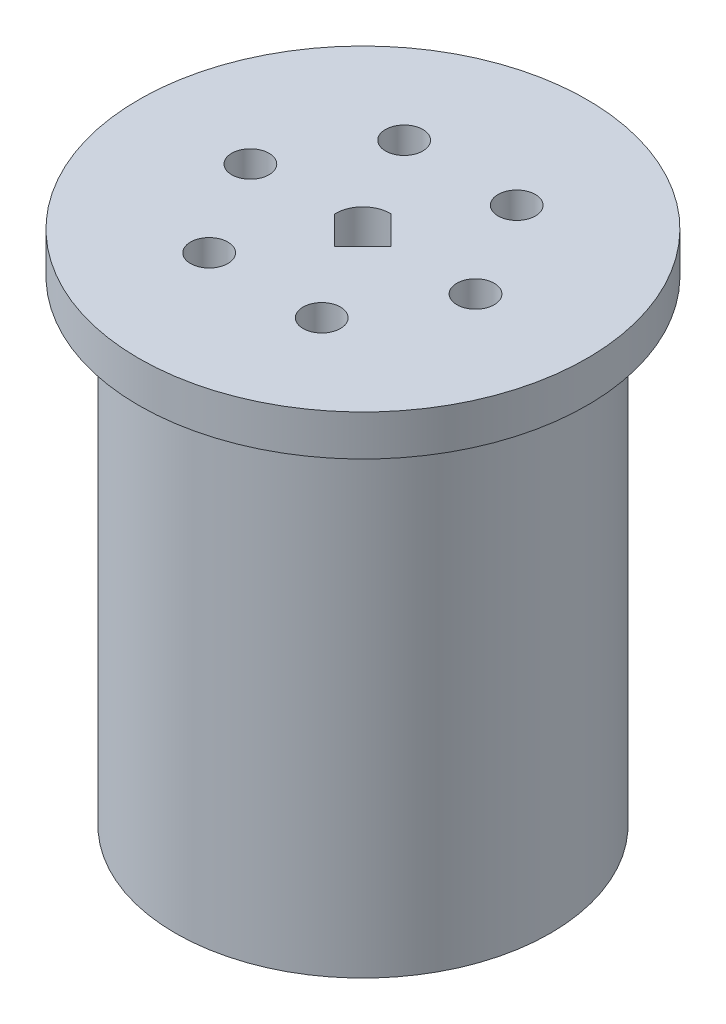
SolidWorks part; units mm, degrees
ref_plane "Front Plane" through (0, 0, 0) normal (0, 0, 1) x (1, 0, 0)
ref_plane "Top Plane" through (0, 0, 0) normal (0, 1, 0) x (1, 0, 0)
ref_plane "Right Plane" through (0, 0, 0) normal (1, 0, 0) x (0, 0, -1)
sketch "Sketch2" plane through (0, 0, 0) normal (0, 1, 0) x (1, 0, 0)
  line L0 (-3.997, -0.1544) -> (0.1585, -4.31)
  line L1 (0.1585, -4.31) -> (4.3141, -0.1544)
  line L2 (0.163, 3.9967) -> (4.3141, -0.1544)
  circle A0 centre (0, 0) radius 27.6
  arc A1 (-3.997, -0.1544) -> (0.163, 3.9967) centre (0, 0) cw
  dimension "D1" = 0
  dimension "D2" = 0
extrude "Boss-Extrude1" add sketch "Sketch2" along normal blind 70 contours A0
extrude "Cut-Extrude1" cut sketch "Sketch2<4>" along normal blind 50 contours L0 L1 L2 A1
sketch "Sketch2<4>" plane through (0, 0, 0) normal (0, 1, 0) x (1, 0, 0) same geometry as "Sketch2"
sketch "Sketch3" plane through (0, 70, 0) normal (0, 1, 0) x (1, 0, 0)
  circle A5 centre (-8.2868, 14.3531) radius 2.75
  circle A6 centre (-16.5735, 0) radius 2.75
  circle A7 centre (-8.2867, -14.3531) radius 2.75
  circle A8 centre (8.2868, -14.3531) radius 2.75
  circle A9 centre (16.5735, 0) radius 2.75
  circle A10 centre (8.2867, 14.3531) radius 2.75
  dimension "D1" = 16.5735
extrude "Cut-Extrude2" cut sketch "Sketch3" against normal blind 110
sketch "Sketch4" plane through (0, 70, 0) normal (0, 1, 0) x (1, 0, 0)
  circle A0 centre (0, 0) radius 33
extrude "Boss-Extrude2" add sketch "Sketch4" along normal blind 6
extrude "Cut-Extrude3" cut sketch "Sketch3<2>" along normal blind 6
sketch "Sketch3<2>" plane through (0, 70, 0) normal (0, 1, 0) x (1, 0, 0) same geometry as "Sketch3"
extrude "Cut-Extrude4" cut sketch "Sketch2<5>" along normal blind 81 contours L2 L1 L0 A1
sketch "Sketch2<5>" plane through (0, 0, 0) normal (0, 1, 0) x (1, 0, 0) same geometry as "Sketch2"
